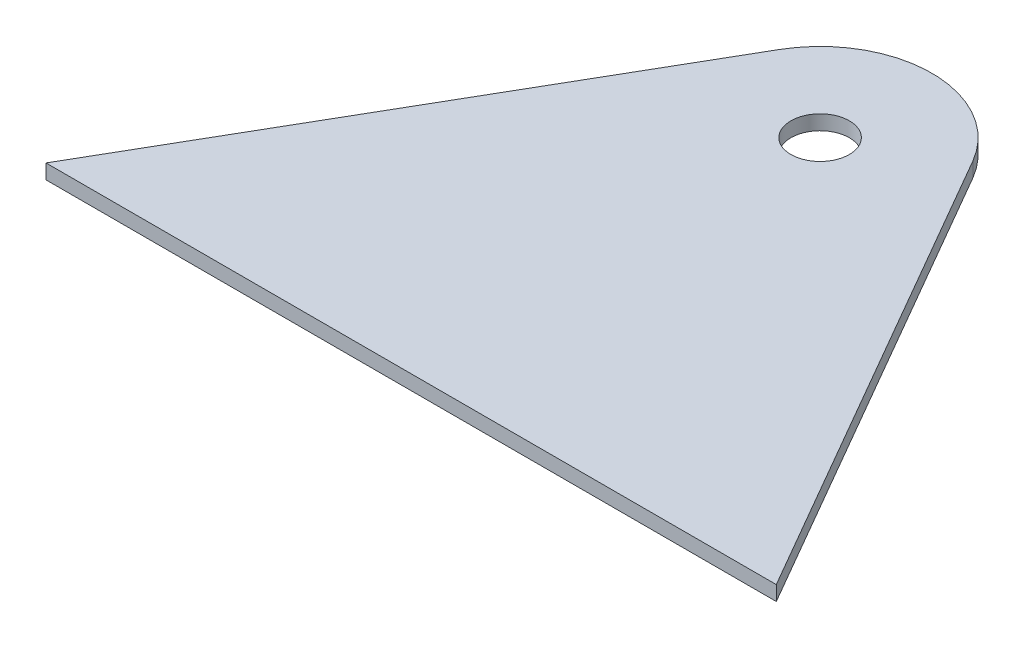
SolidWorks part; units mm, degrees
ref_plane "Front Plane" through (0, 0, 0) normal (0, 0, 1) x (1, 0, 0)
ref_plane "Top Plane" through (0, 0, 0) normal (0, 1, 0) x (1, 0, 0)
ref_plane "Right Plane" through (0, 0, 0) normal (1, 0, 0) x (0, 0, -1)
sketch "Sketch1" plane through (0, 0, 0) normal (0, 1, 0) x (1, 0, 0)
  line L0 (-79.375, 0) -> (79.375, 0)
  line L1 (0, 0) -> (0, 88.9) construction
  line L2 (-79.375, 0) -> (-21.0364, 101.0454)
  line L3 (21.0364, 101.0454) -> (79.375, 0)
  circle A0 centre (0, 88.9) radius 6.35
  arc A1 (-21.0364, 101.0454) -> (21.0364, 101.0454) centre (0, 88.9) cw
  point P4 (0, 0)
  dimension "D3" = 12.7
  dimension "D4" = 60
  dimension "D1" = 158.75
  dimension "D2" = 88.9
extrude "Boss-Extrude1" add sketch "Sketch1" along normal blind 3.1902
